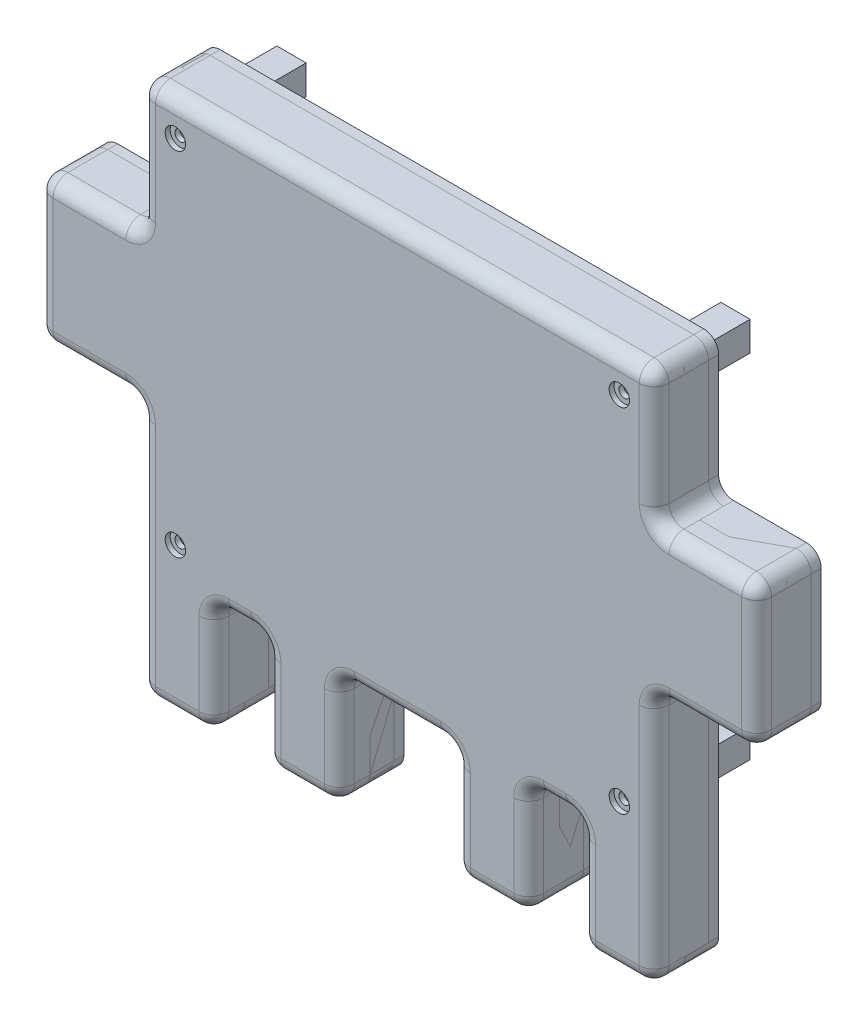
SolidWorks part; units mm, degrees
ref_plane "Front Plane" through (0, 0, 0) normal (0, 0, 1) x (1, 0, 0)
ref_plane "Top Plane" through (0, 0, 0) normal (0, 1, 0) x (1, 0, 0)
ref_plane "Right Plane" through (0, 0, 0) normal (1, 0, 0) x (0, 0, -1)
sketch "圖片" plane through (0, 0, 0) normal (0, 0, 1) x (1, 0, 0)
  line L0 (219.174, 501.4094) -> (1128.5073, 501.4094) construction
sketch "padTop" plane through (0, 0, 0) normal (0, 0, 1) x (1, 0, 0)
  line L0 (36.7115, 8.5135) -> (50.8115, 8.5135)
  line L1 (36.7115, 27.6135) -> (50.8115, 27.6135)
  line L2 (36.7115, 27.6135) -> (36.7115, 13.5135)
  line L3 (36.7115, 13.5135) -> (50.8115, 13.5135)
  line L4 (50.8115, 27.6135) -> (50.8115, 13.5135)
  line L5 (36.7115, 27.6135) -> (50.8115, 13.5135) construction
  line L6 (36.7115, 13.5135) -> (50.8115, 27.6135) construction
  line L7 (36.7115, 8.5135) -> (36.7115, -5.5865)
  line L8 (36.7115, -5.5865) -> (50.8115, -5.5865)
  line L9 (50.8115, 8.5135) -> (50.8115, -5.5865)
  line L10 (36.7115, 8.5135) -> (50.8115, -5.5865) construction
  line L11 (36.7115, -5.5865) -> (50.8115, 8.5135) construction
  line L12 (94.0115, 8.5135) -> (108.1115, 8.5135)
  line L13 (94.0115, 27.6135) -> (108.1115, 27.6135)
  line L14 (94.0115, 27.6135) -> (94.0115, 13.5135)
  line L15 (94.0115, 13.5135) -> (108.1115, 13.5135)
  line L16 (108.1115, 27.6135) -> (108.1115, 13.5135)
  line L17 (94.0115, 27.6135) -> (108.1115, 13.5135) construction
  line L18 (94.0115, 13.5135) -> (108.1115, 27.6135) construction
  line L19 (94.0115, 8.5135) -> (94.0115, -5.5865)
  line L20 (94.0115, -5.5865) -> (108.1115, -5.5865)
  line L21 (108.1115, 8.5135) -> (108.1115, -5.5865)
  line L22 (94.0115, 8.5135) -> (108.1115, -5.5865) construction
  line L23 (94.0115, -5.5865) -> (108.1115, 8.5135) construction
  line L24 (55.8115, 8.5135) -> (69.9115, 8.5135)
  line L25 (55.8115, 27.6135) -> (69.9115, 27.6135)
  line L26 (55.8115, 27.6135) -> (55.8115, 13.5135)
  line L27 (55.8115, 13.5135) -> (69.9115, 13.5135)
  line L28 (69.9115, 27.6135) -> (69.9115, 13.5135)
  line L29 (55.8115, 27.6135) -> (69.9115, 13.5135) construction
  line L30 (55.8115, 13.5135) -> (69.9115, 27.6135) construction
  line L31 (55.8115, 8.5135) -> (55.8115, -5.5865)
  line L32 (55.8115, -5.5865) -> (69.9115, -5.5865)
  line L33 (69.9115, 8.5135) -> (69.9115, -5.5865)
  line L34 (55.8115, 8.5135) -> (69.9115, -5.5865) construction
  line L35 (55.8115, -5.5865) -> (69.9115, 8.5135) construction
  line L36 (74.9115, 8.5135) -> (89.0115, 8.5135)
  line L37 (74.9115, 27.6135) -> (89.0115, 27.6135)
  line L38 (74.9115, 27.6135) -> (74.9115, 13.5135)
  line L39 (74.9115, 13.5135) -> (89.0115, 13.5135)
  line L40 (89.0115, 27.6135) -> (89.0115, 13.5135)
  line L41 (74.9115, 27.6135) -> (89.0115, 13.5135) construction
  line L42 (74.9115, 13.5135) -> (89.0115, 27.6135) construction
  line L43 (74.9115, 8.5135) -> (74.9115, -5.5865)
  line L44 (74.9115, -5.5865) -> (89.0115, -5.5865)
  line L45 (89.0115, 8.5135) -> (89.0115, -5.5865)
  line L46 (74.9115, 8.5135) -> (89.0115, -5.5865) construction
  line L47 (74.9115, -5.5865) -> (89.0115, 8.5135) construction
  line L48 (62.8615, 20.5635) -> (81.9615, 20.5635) construction
  line L49 (72.4115, 165.3189) -> (72.4115, -124.1918) construction
  line L50 (81.9615, 20.5635) -> (81.9615, 1.4635) construction
  line L51 (26.7144, 11.0135) -> (137.2086, 11.0135) construction
  line L52 (10.3648, 43.6826) -> (10.3648, 14.487) construction
  line L53 (33.7615, 30.5635) -> (111.0615, 30.5635)
  line L54 (33.7615, 30.5635) -> (33.7615, -8.5365)
  line L55 (33.7615, -8.5365) -> (111.0615, -8.5365)
  line L56 (111.0615, 30.5635) -> (111.0615, -8.5365)
  line L57 (33.7615, 30.5635) -> (111.0615, -8.5365) construction
  line L58 (33.7615, -8.5365) -> (111.0615, 30.5635) construction
  line L59 (20.6927, 70.4526) -> (124.1303, 70.4526)
  line L60 (20.6927, 70.4526) -> (20.6927, -14.4886)
  line L61 (20.6927, -14.4886) -> (124.1303, -14.4886)
  line L62 (124.1303, 70.4526) -> (124.1303, -14.4886)
  line L63 (20.6927, 70.4526) -> (124.1303, -14.4886) construction
  line L64 (20.6927, -14.4886) -> (124.1303, 70.4526) construction
  line L65 (20.6927, 43.6826) -> (0.037, 43.6826)
  line L66 (20.6927, 43.6826) -> (20.6927, 14.487)
  line L67 (20.6927, 14.487) -> (0.037, 14.487)
  line L68 (0.037, 43.6826) -> (0.037, 14.487)
  line L69 (124.1303, 43.5052) -> (144.7861, 43.5052)
  line L70 (124.1303, 43.5052) -> (124.1303, 14.3095)
  line L71 (124.1303, 14.3095) -> (144.7861, 14.3095)
  line L72 (144.7861, 43.5052) -> (144.7861, 14.3095)
  line L73 (20.6927, -14.4886) -> (35.4563, -14.4886)
  line L74 (20.6927, -14.4886) -> (20.6927, -37.1354)
  line L75 (20.6927, -37.1354) -> (35.4563, -37.1354)
  line L76 (35.4563, -14.4886) -> (35.4563, -37.1354)
  line L77 (45.9563, -14.4886) -> (60.7199, -14.4886)
  line L78 (45.9563, -14.4886) -> (45.9563, -37.1354)
  line L79 (45.9563, -37.1354) -> (60.7199, -37.1354)
  line L80 (60.7199, -14.4886) -> (60.7199, -37.1354)
  line L81 (84.1032, -14.4886) -> (98.8668, -14.4886)
  line L82 (84.1032, -14.4886) -> (84.1032, -37.1354)
  line L83 (84.1032, -37.1354) -> (98.8668, -37.1354)
  line L84 (98.8668, -14.4886) -> (98.8668, -37.1354)
  line L85 (124.1303, -14.4886) -> (109.3668, -14.4886)
  line L86 (124.1303, -14.4886) -> (124.1303, -37.1354)
  line L87 (124.1303, -37.1354) -> (109.3668, -37.1354)
  line L88 (109.3668, -14.4886) -> (109.3668, -37.1354)
  line L89 (37.3633, 56.7764) -> (48.4633, 56.7764)
  line L90 (37.3633, 56.7764) -> (37.3633, 45.6764)
  line L91 (37.3633, 45.6764) -> (48.4633, 45.6764)
  line L92 (48.4633, 56.7764) -> (48.4633, 45.6764)
  line L93 (37.3633, 56.7764) -> (48.4633, 45.6764) construction
  line L94 (37.3633, 45.6764) -> (48.4633, 56.7764) construction
  line L95 (96.5235, 56.7764) -> (107.6235, 56.7764)
  line L96 (96.5235, 56.7764) -> (96.5235, 45.6764)
  line L97 (96.5235, 45.6764) -> (107.6235, 45.6764)
  line L98 (107.6235, 56.7764) -> (107.6235, 45.6764)
  line L99 (96.5235, 56.7764) -> (107.6235, 45.6764) construction
  line L100 (96.5235, 45.6764) -> (107.6235, 56.7764) construction
  line L101 (7.787, 36.1348) -> (21.887, 36.1348)
  line L102 (7.787, 36.1348) -> (7.787, 22.0348)
  line L103 (7.787, 22.0348) -> (21.887, 22.0348)
  line L104 (21.887, 36.1348) -> (21.887, 22.0348)
  line L105 (7.787, 36.1348) -> (21.887, 22.0348) construction
  line L106 (7.787, 22.0348) -> (21.887, 36.1348) construction
  line L107 (-985.163, 29.0848) -> (49014.837, 29.0848) construction
  line L108 (24.837, 38.7911) -> (4.837, 38.7911)
  line L109 (24.837, 38.7911) -> (24.837, 19.3785)
  line L110 (24.837, 19.3785) -> (4.837, 19.3785)
  line L111 (4.837, 38.7911) -> (4.837, 19.3785)
  line L112 (24.837, 38.7911) -> (4.837, 19.3785) construction
  line L113 (24.837, 19.3785) -> (4.837, 38.7911) construction
  line L114 (43.7615, 20.5635) -> (62.8615, 20.5635) construction
  line L115 (32.9133, 61.2264) -> (52.9133, 61.2264)
  line L116 (32.9133, 61.2264) -> (32.9133, 41.2264)
  line L117 (32.9133, 41.2264) -> (52.9133, 41.2264)
  line L118 (52.9133, 61.2264) -> (52.9133, 41.2264)
  line L119 (32.9133, 61.2264) -> (52.9133, 41.2264) construction
  line L120 (32.9133, 41.2264) -> (52.9133, 61.2264) construction
  line L121 (92.0735, 61.2264) -> (112.0735, 61.2264)
  line L122 (92.0735, 61.2264) -> (92.0735, 41.2264)
  line L123 (92.0735, 41.2264) -> (112.0735, 41.2264)
  line L124 (112.0735, 61.2264) -> (112.0735, 41.2264)
  line L125 (92.0735, 61.2264) -> (112.0735, 41.2264) construction
  line L126 (92.0735, 41.2264) -> (112.0735, 61.2264) construction
  line L127 (81.9615, 20.5635) -> (101.0615, 20.5635) construction
  line L128 (53.3115, 20.5635) -> (53.3115, 3.2406) construction
  line L129 (91.5115, 20.5635) -> (91.5115, 3.2406) construction
  circle A0 centre (129.9861, 29.0848) radius 3.75
  point P0 (43.7615, 20.5635)
  point P5 (43.7615, 1.4635)
  point P10 (72.4115, 11.0135)
  point P11 (101.0615, 20.5635)
  point P16 (101.0615, 1.4635)
  point P21 (62.8615, 20.5635)
  point P26 (62.8615, 1.4635)
  point P31 (81.9615, 20.5635)
  point P36 (81.9615, 1.4635)
  point P45 (72.4115, 20.5635)
  point P46 (72.4115, 20.5635)
  point P50 (81.9615, 11.0135)
  point P51 (72.4115, 11.0135)
  point P56 (72.4115, 27.982)
  point P83 (42.9133, 51.2264)
  point P88 (102.0735, 51.2264)
  point P95 (14.837, 29.0848)
  point P96 (14.837, 29.0848)
  point P101 (10.3648, 29.0848)
  point P107 (0.037, 29.0848)
  point P109 (129.9861, 29.0848)
  point P110 (102.0735, 51.2264)
  point P111 (42.9133, 51.2264)
  point P128 (53.3115, 11.0135)
  point P129 (91.5115, 11.0135)
  dimension "D8" = 10.5
  dimension "D16" = 7.5
  dimension "D1" = 14.1
  dimension "D2" = 19.1
  dimension "D3" = 19.1
  dimension "D4" = 19.1
  dimension "D5" = 19.1
  dimension "D6" = 10
  dimension "D7" = 10
  dimension "D9" = 10.5
  dimension "D10" = 11.1
  dimension "D11" = 14.1
  dimension "D12" = 20
  dimension "D13" = 14.8
  dimension "D14" = 14.8
  dimension "D15" = 20
  dimension "D17" = 103.4376
sketch "RP2024" plane through (0, 0, 0) normal (0, 0, 1) x (1, 0, 0)
  line L1 (60.9115, 67.8246) -> (83.9115, 67.8246)
  line L2 (60.9115, 67.8246) -> (60.9115, 13.8246)
  line L3 (60.9115, 13.8246) -> (83.9115, 13.8246)
  line L4 (83.9115, 67.8246) -> (83.9115, 13.8246)
  line L5 (60.9115, 67.8246) -> (83.9115, 13.8246) construction
  line L6 (60.9115, 13.8246) -> (83.9115, 67.8246) construction
  line L7 (72.4115, 165.3189) -> (72.4115, -124.1918) construction
  point P0 (72.4115, 40.8246)
  dimension "D1" = 54
  dimension "D2" = 23
sketch "numb" plane through (0, 0, 0) normal (0, 0, 1) x (1, 0, 0)
  circle A0 centre (129.9861, 29.0848) radius 17.5
  dimension "D1" = 35
extrude "填料-伸長1" add sketch "padTop" along normal blind 7.8 contours L109 L110 L66 L60 L61 L62 L59 L108 L115 L118 L117 L116 L53 L56 L55 L54 L121 L124 L123 L122 | L72 L69 L62 L71 A0 | L111 L108 L60 L65 L68 L67 L66 L110 | L124 L121 L122 L123 L95 L98 L97 L96 | L118 L115 L116 L117 L89 L92 L91 L90 | L74 L73 L76 L75 | L78 L77 L80 L79 | L82 L81 L84 L83 | L86 L85 L88 L87 region at (73.216, 34.6583, 0) region at (20.3351, 41.2368, 0) region at (134.8117, 28.8933, 0) region at (42.9133, 60.9435, 0) region at (102.0735, 60.9435, 0)
extrude "填料-伸長4" add sketch "padTop<8>" against normal blind 2 contours L109 L110 L66 L60 L61 L62 L59 L108 L115 L118 L117 L116 L53 L56 L55 L54 L121 L124 L123 L122 | L72 L69 L62 L71 A0 | L111 L108 L60 L65 L68 L67 L66 L110 | L76 L61 L74 L75 | L80 L61 L78 L79 | L84 L61 L82 L83 | L61 L88 L87 L86 | L56 L53 L54 L55 L1 L4 L3 L2 L0 L9 L8 L7 L13 L16 L15 L14 L12 L21 L20 L19 L25 L28 L27 L26 L24 L33 L32 L31 L37 L40 L39 L38 L36 L45 L44 L43 | L108 L111 L110 L60 L103 L102 L101 L66 | L110 L109 L108 L66 L101 L104 L103 L60 region at (72.4115, 11.0135, 0) region at (73.216, 34.6583, 0) region at (20.3351, 41.2368, 0) region at (134.8117, 28.8933, 0) region at (23.1553, 29.0848, 0) region at (20.442, 37.4629, 0) region at (116.7485, -25.812, 0) region at (28.0745, -25.812, 0) region at (91.485, -25.812, 0) region at (53.3381, -25.812, 0)
sketch "padTop<8>" plane through (0, 0, 0) normal (0, 0, 1) x (1, 0, 0) same geometry as "padTop"
sketch "草圖2" plane through (0, 0, 0) normal (0, 0, 1) x (1, 0, 0)
  line L0 (20.6927, 43.6826) -> (0.037, 43.6826)
  line L5 (0.037, 43.6826) -> (0.037, 14.487)
  line L6 (0.037, 14.487) -> (20.6927, 14.487)
  line L31 (20.6927, 14.487) -> (20.6927, -37.1354)
  line L32 (20.6927, -37.1354) -> (35.4563, -37.1354)
  line L33 (35.4563, -37.1354) -> (35.4563, -14.4886)
  line L34 (35.4563, -14.4886) -> (45.9563, -14.4886)
  line L35 (45.9563, -14.4886) -> (45.9563, -37.1354)
  line L36 (45.9563, -37.1354) -> (60.7199, -37.1354)
  line L37 (60.7199, -37.1354) -> (60.7199, -14.4886)
  line L38 (60.7199, -14.4886) -> (84.1032, -14.4886)
  line L39 (84.1032, -14.4886) -> (84.1032, -37.1354)
  line L40 (84.1032, -37.1354) -> (98.8668, -37.1354)
  line L41 (98.8668, -37.1354) -> (98.8668, -14.4886)
  line L42 (98.8668, -14.4886) -> (109.3668, -14.4886)
  line L43 (109.3668, -14.4886) -> (109.3668, -37.1354)
  line L44 (109.3668, -37.1354) -> (124.1303, -37.1354)
  line L45 (124.1303, -37.1354) -> (124.1303, 14.3095)
  line L46 (124.1303, 14.3095) -> (144.7861, 14.3095)
  line L47 (144.7861, 14.3095) -> (144.7861, 43.5052)
  line L48 (144.7861, 43.5052) -> (124.1303, 43.5052)
  line L49 (124.1303, 43.5052) -> (124.1303, 70.4526)
  line L50 (124.1303, 70.4526) -> (20.6927, 70.4526)
  line L51 (20.6927, 70.4526) -> (20.6927, 43.6826)
extrude "填料-伸長6" add sketch "草圖2" along normal blind 11 separate body
fillet "圓角2" radius 3 48 edges at (72.4115, 70.4526, 11) (124.1303, 56.9789, 11) (134.4582, 43.5052, 11) (144.7861, 28.9073, 11) (134.4582, 14.3095, 11) (124.1303, -11.4129, 11) (116.7485, -37.1354, 11) (109.3668, -25.812, 11) (104.1168, -14.4886, 11) (98.8668, -25.812, 11) (91.485, -37.1354, 11) (84.1032, -25.812, 11) (72.4115, -14.4886, 11) (60.7199, -25.812, 11) (53.3381, -37.1354, 11) (45.9563, -25.812, 11) (40.7063, -14.4886, 11) (35.4563, -25.812, 11) (28.0745, -37.1354, 11) (20.6927, -11.3242, 11) (10.3648, 14.487, 11) (0.037, 29.0848, 11) (10.3648, 43.6826, 11) (20.6927, 57.0676, 11) (20.6927, 70.4526, 5.5) (20.6927, 43.6826, 5.5) (0.037, 43.6826, 5.5) (35.4563, -14.4886, 5.5) (35.4563, -37.1354, 5.5) (0.037, 14.487, 5.5) (20.6927, 14.487, 5.5) (20.6927, -37.1354, 5.5) (45.9563, -14.4886, 5.5) (45.9563, -37.1354, 5.5) (60.7199, -37.1354, 5.5) (60.7199, -14.4886, 5.5) (98.8668, -14.4886, 5.5) (98.8668, -37.1354, 5.5) (84.1032, -37.1354, 5.5) (84.1032, -14.4886, 5.5) (109.3668, -14.4886, 5.5) (109.3668, -37.1354, 5.5) (124.1303, -37.1354, 5.5) (124.1303, 14.3095, 5.5) (144.7861, 14.3095, 5.5) (144.7861, 43.5052, 5.5) (124.1303, 43.5052, 5.5) (124.1303, 70.4526, 5.5)
shell "薄殼1" thickness 2 removed face at (72.4115, -0.4642, 0)
fillet "圓角4" radius 3 48 edges at (20.6927, 57.0676, 7.8) (10.3648, 14.487, 7.8) (40.7063, -14.4886, 7.8) (124.1303, 56.9789, 7.8) (20.6927, 70.4526, 2.9) (0.037, 43.6826, 2.9) (10.3648, 43.6826, 7.8) (20.6927, 43.6826, 2.9) (0.037, 29.0848, 7.8) (0.037, 14.487, 2.9) (20.6927, 14.487, 2.9) (20.6927, -11.3242, 7.8) (20.6927, -37.1354, 2.9) (35.4563, -37.1354, 2.9) (28.0745, -37.1354, 7.8) (35.4563, -25.812, 7.8) (45.9563, -14.4886, 2.9) (72.4115, 70.4526, 7.8) (124.1303, 70.4526, 2.9) (124.1303, 43.5052, 2.9) (134.4582, 43.5052, 7.8) (144.7861, 43.5052, 2.9) (144.7861, 28.9073, 7.8) (144.7861, 14.3095, 2.9) (124.1303, 14.3095, 2.9) (124.1303, -37.1354, 2.9) (109.3668, -37.1354, 2.9) (98.8668, -14.4886, 2.9) (84.1032, -37.1354, 2.9) (98.8668, -37.1354, 2.9) (109.3668, -14.4886, 2.9) (134.4582, 14.3095, 7.8) (109.3668, -25.812, 7.8) (116.7485, -37.1354, 7.8) (124.1303, -11.4129, 7.8) (104.1168, -14.4886, 7.8) (98.8668, -25.812, 7.8) (91.485, -37.1354, 7.8) (84.1032, -14.4886, 2.9) (60.7199, -14.4886, 2.9) (53.3381, -37.1354, 7.8) (45.9563, -25.812, 7.8) (60.7199, -25.812, 7.8) (84.1032, -25.812, 7.8) (72.4115, -14.4886, 7.8) (35.4563, -14.4886, 2.9) (45.9563, -37.1354, 2.9) (60.7199, -37.1354, 2.9)
ref_plane "平面1" through (0, 0, 9) normal (0, 0, -1) x (-1, 0, 0)
sketch "草圖4" plane through (0, 0, 9) normal (0, 0, -1) x (-1, 0, 0)
  line L0 (-92.5115, 16.0135) -> (-90.5115, 16.0135)
  line L1 (-54.3115, 16.0135) -> (-52.3115, 16.0135)
  line L4 (-54.3115, 16.0135) -> (-54.3115, 6.0135)
  line L5 (-54.3115, 6.0135) -> (-52.3115, 6.0135)
  line L6 (-52.3115, 16.0135) -> (-52.3115, 6.0135)
  line L7 (-54.3115, 16.0135) -> (-52.3115, 6.0135) construction
  line L8 (-54.3115, 6.0135) -> (-52.3115, 16.0135) construction
  line L9 (-58.3115, 12.0135) -> (-48.3115, 12.0135)
  line L10 (-58.3115, 12.0135) -> (-58.3115, 10.0135)
  line L11 (-58.3115, 10.0135) -> (-48.3115, 10.0135)
  line L12 (-48.3115, 12.0135) -> (-48.3115, 10.0135)
  line L13 (-58.3115, 12.0135) -> (-48.3115, 10.0135) construction
  line L14 (-58.3115, 10.0135) -> (-48.3115, 12.0135) construction
  line L15 (-92.5115, 16.0135) -> (-92.5115, 6.0135)
  line L16 (-92.5115, 6.0135) -> (-90.5115, 6.0135)
  line L17 (-90.5115, 16.0135) -> (-90.5115, 6.0135)
  line L18 (-92.5115, 16.0135) -> (-90.5115, 6.0135) construction
  line L19 (-92.5115, 6.0135) -> (-90.5115, 16.0135) construction
  line L20 (-96.5115, 12.0135) -> (-86.5115, 12.0135)
  line L21 (-96.5115, 12.0135) -> (-96.5115, 10.0135)
  line L22 (-96.5115, 10.0135) -> (-86.5115, 10.0135)
  line L23 (-86.5115, 12.0135) -> (-86.5115, 10.0135)
  line L24 (-96.5115, 12.0135) -> (-86.5115, 10.0135) construction
  line L25 (-96.5115, 10.0135) -> (-86.5115, 12.0135) construction
  point P0 (-53.3115, 11.0135)
  point P5 (-53.3115, 11.0135)
  point P11 (-91.5115, 11.0135)
  point P17 (-91.5115, 11.0135)
  dimension "D1" = 10
  dimension "D2" = 2
ref_plane "平面2" through (0, 0, -2) normal (0, 0, 1) x (1, 0, 0)
sketch "草圖5" plane through (0, 0, -2) normal (0, 0, 1) x (1, 0, 0)
  line L1 (26.7427, 64.4026) -> (28.6427, 64.4026)
  line L2 (26.7427, 64.4026) -> (26.7427, 62.5026)
  line L3 (26.7427, 62.5026) -> (28.6427, 62.5026)
  line L4 (28.6427, 64.4026) -> (28.6427, 62.5026)
  line L5 (26.7427, 64.4026) -> (28.6427, 62.5026) construction
  line L6 (26.7427, 62.5026) -> (28.6427, 64.4026) construction
  line L7 (20.6927, 70.4526) -> (20.6927, -14.4886) construction
  line L8 (26.7427, -6.5386) -> (28.6427, -6.5386)
  line L9 (24.7427, 66.4026) -> (30.6427, 66.4026)
  line L10 (24.7427, 66.4026) -> (24.7427, 60.5026)
  line L11 (24.7427, 60.5026) -> (30.6427, 60.5026)
  line L12 (30.6427, 66.4026) -> (30.6427, 60.5026)
  line L13 (24.7427, 66.4026) -> (30.6427, 60.5026) construction
  line L14 (24.7427, 60.5026) -> (30.6427, 66.4026) construction
  line L15 (26.7427, -6.5386) -> (26.7427, -8.4386)
  line L16 (26.7427, -8.4386) -> (28.6427, -8.4386)
  line L17 (28.6427, -6.5386) -> (28.6427, -8.4386)
  line L18 (26.7427, -6.5386) -> (28.6427, -8.4386) construction
  line L19 (26.7427, -8.4386) -> (28.6427, -6.5386) construction
  line L20 (24.7427, -4.5386) -> (30.6427, -4.5386)
  line L21 (24.7427, -4.5386) -> (24.7427, -10.4386)
  line L22 (24.7427, -10.4386) -> (30.6427, -10.4386)
  line L23 (30.6427, -4.5386) -> (30.6427, -10.4386)
  line L24 (24.7427, -4.5386) -> (30.6427, -10.4386) construction
  line L25 (24.7427, -10.4386) -> (30.6427, -4.5386) construction
  line L26 (116.1803, -6.5386) -> (118.0803, -6.5386)
  line L27 (116.1803, -6.5386) -> (116.1803, -8.4386)
  line L28 (116.1803, -8.4386) -> (118.0803, -8.4386)
  line L29 (118.0803, -6.5386) -> (118.0803, -8.4386)
  line L30 (116.1803, -6.5386) -> (118.0803, -8.4386) construction
  line L31 (116.1803, -8.4386) -> (118.0803, -6.5386) construction
  line L32 (114.1803, -4.5386) -> (120.0803, -4.5386)
  line L33 (114.1803, -4.5386) -> (114.1803, -10.4386)
  line L34 (114.1803, -10.4386) -> (120.0803, -10.4386)
  line L35 (120.0803, -4.5386) -> (120.0803, -10.4386)
  line L36 (114.1803, -4.5386) -> (120.0803, -10.4386) construction
  line L37 (114.1803, -10.4386) -> (120.0803, -4.5386) construction
  line L38 (116.1803, 64.4026) -> (118.0803, 64.4026)
  line L39 (116.1803, 64.4026) -> (116.1803, 62.5026)
  line L40 (116.1803, 62.5026) -> (118.0803, 62.5026)
  line L41 (118.0803, 64.4026) -> (118.0803, 62.5026)
  line L42 (116.1803, 64.4026) -> (118.0803, 62.5026) construction
  line L43 (116.1803, 62.5026) -> (118.0803, 64.4026) construction
  line L44 (114.1803, 66.4026) -> (120.0803, 66.4026)
  line L45 (114.1803, 66.4026) -> (114.1803, 60.5026)
  line L46 (114.1803, 60.5026) -> (120.0803, 60.5026)
  line L47 (120.0803, 66.4026) -> (120.0803, 60.5026)
  line L48 (114.1803, 66.4026) -> (120.0803, 60.5026) construction
  line L49 (114.1803, 60.5026) -> (120.0803, 66.4026) construction
  line L50 (52.3115, 16.0135) -> (54.3115, 16.0135)
  line L51 (20.6927, 70.4526) -> (124.1303, 70.4526) construction
  line L52 (20.6927, -14.4886) -> (124.1303, -14.4886) construction
  line L53 (124.1303, 70.4526) -> (124.1303, -14.4886) construction
  line L54 (52.3115, 16.0135) -> (52.3115, 6.0135)
  line L55 (52.3115, 6.0135) -> (54.3115, 6.0135)
  line L56 (54.3115, 16.0135) -> (54.3115, 6.0135)
  line L57 (48.3115, 12.0135) -> (58.3115, 12.0135)
  line L58 (48.3115, 12.0135) -> (48.3115, 10.0135)
  line L59 (48.3115, 10.0135) -> (58.3115, 10.0135)
  line L60 (58.3115, 12.0135) -> (58.3115, 10.0135)
  line L61 (86.5115, 12.0135) -> (96.5115, 12.0135)
  line L62 (86.5115, 12.0135) -> (86.5115, 10.0135)
  line L63 (86.5115, 10.0135) -> (96.5115, 10.0135)
  line L64 (96.5115, 12.0135) -> (96.5115, 10.0135)
  line L65 (92.5115, 16.0135) -> (90.5115, 16.0135)
  line L66 (92.5115, 16.0135) -> (92.5115, 6.0135)
  line L67 (92.5115, 6.0135) -> (90.5115, 6.0135)
  line L68 (90.5115, 16.0135) -> (90.5115, 6.0135)
  point P0 (27.6927, 63.4526)
  point P5 (27.6927, 63.4526)
  point P14 (27.6927, -7.4886)
  point P19 (27.6927, -7.4886)
  point P24 (117.1303, -7.4886)
  point P29 (117.1303, -7.4886)
  point P34 (117.1303, 63.4526)
  point P39 (117.1303, 63.4526)
  dimension "D1" = 1.9
  dimension "D2" = 7
  dimension "D3" = 7
  dimension "D4" = 5.9
  dimension "D5" = 7
  dimension "D6" = 7
extrude "填料-伸長9" add sketch "草圖5" against normal blind 11.46 contours L61 L68 L63 L66 | L68 L61 L62 L63 | L65 L68 L61 L66 | L63 L68 L67 L66 | L61 L66 L63 L64 | L54 L59 L56 L57 | L58 L59 L54 L57 | L54 L57 L56 L50 | L60 L57 L56 L59 | L59 L54 L55 L56 region at (53.3115, 14.0135, -2) region at (53.3115, 11.0135, -2) region at (50.3115, 11.0135, -2) region at (56.3115, 11.0135, -2) region at (53.3115, 8.0135, -2) region at (88.5115, 11.0135, -2) region at (91.5115, 14.0135, -2) region at (91.5115, 11.0135, -2) region at (94.5115, 11.0135, -2) region at (91.5115, 8.0135, -2)
ref_plane "平面3" through (0, 0, 11) normal (0, 0, 1) x (1, 0, 0)
sketch "草圖7" plane through (0, 0, 11) normal (0, 0, 1) x (1, 0, 0)
  line L0 (26.7427, -6.5386) -> (28.6427, -8.4386) construction
  circle A0 centre (27.6927, 63.4526) radius 2.05
  circle A1 centre (117.1303, 63.4526) radius 2.05
  circle A2 centre (117.1303, -7.4886) radius 2.05
  circle A3 centre (27.6927, -7.4886) radius 2.05
  circle A4 centre (27.6927, 63.4526) radius 1.1
  circle A5 centre (117.1303, 63.4526) radius 1.1
  circle A6 centre (117.1303, -7.4886) radius 1.1
  circle A7 centre (27.6927, -7.4886) radius 1.1
  dimension "D1" = 4.1
  dimension "D2" = 2.2
extrude "除料-伸長1" cut sketch "草圖7" against normal up to next (2 mm away) contours A6 | A4 | A5 | A7
extrude "除料-伸長2" cut sketch "草圖7<4>" against normal blind 1
sketch "草圖7<4>" plane through (0, 0, 11) normal (0, 0, 1) x (1, 0, 0) same geometry as "草圖7"
ref_plane "平面4" through (0, 0, -2) normal (0, 0, -1) x (-1, 0, 0)
sketch "草圖8" plane through (0, 0, -2) normal (0, 0, -1) x (-1, 0, 0)
  line L1 (-137.5861, 35.1348) -> (-122.3861, 35.1348)
  line L2 (-137.5861, 35.1348) -> (-137.5861, 23.0348)
  line L3 (-137.5861, 23.0348) -> (-122.3861, 23.0348)
  line L4 (-122.3861, 35.1348) -> (-122.3861, 23.0348)
  line L5 (-137.5861, 35.1348) -> (-122.3861, 23.0348) construction
  line L6 (-137.5861, 23.0348) -> (-122.3861, 35.1348) construction
  point P0 (-129.9861, 29.0848)
  dimension "D1" = 15.2
  dimension "D2" = 12.1
extrude "除料-伸長3" cut sketch "草圖8" against normal blind 7.4
extrude "填料-伸長11" add sketch "草圖5<4>" against normal blind 10.4 contours L47 L44 L45 L46 L38 L41 L40 L39 | L35 L32 L33 L34 L26 L29 L28 L27 | L23 L20 L21 L22 L8 L17 L16 L15 | L12 L9 L10 L11 L1 L4 L3 L2 region at (27.6927, 66.3191, -2) region at (27.6927, -4.622, -2) region at (117.1303, -4.622, -2) region at (117.1303, 66.3191, -2)
sketch "草圖5<4>" plane through (0, 0, -2) normal (0, 0, 1) x (1, 0, 0) same geometry as "草圖5"
extrude "除料-伸長4" cut sketch "padTop<9>" along normal blind 5 contours L124 L121 L122 L123 L95 L98 L97 L96 | L118 L115 L116 L117 L89 L92 L91 L90 region at (42.9133, 60.9435, 0) region at (102.0735, 60.9435, 0)
sketch "padTop<9>" plane through (0, 0, 0) normal (0, 0, 1) x (1, 0, 0) same geometry as "padTop"
chamfer "導角1" distance 3 angle 45 8 edges at (117.1303, -10.4386, -2) (114.1803, 63.4526, -2) (117.1303, 60.5026, -2) (30.6427, 63.4526, -2) (27.6927, 60.5026, -2) (27.6927, -4.5386, -2) (27.6927, -10.4386, -2) (117.1303, -4.5386, -2)
